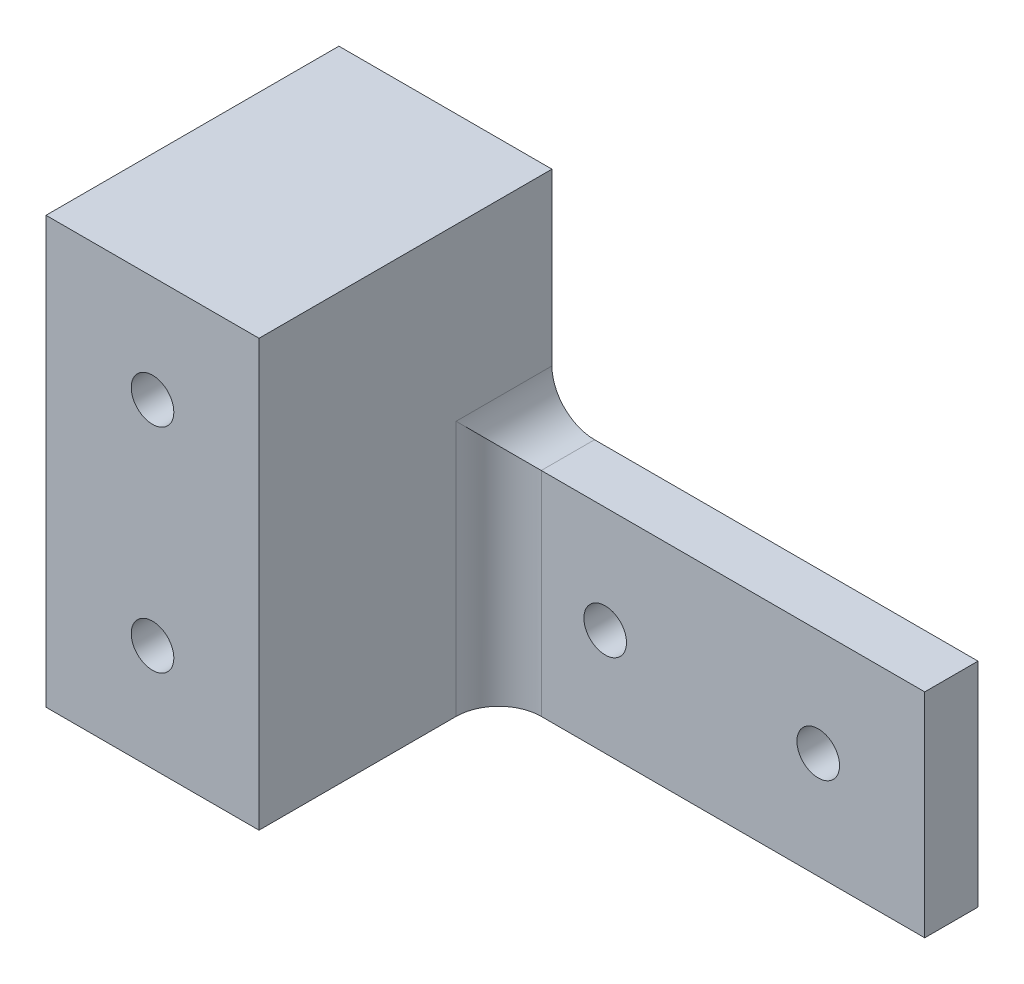
SolidWorks part; units mm, degrees
ref_plane "Front Plane" through (0, 0, 0) normal (0, 0, 1) x (1, 0, 0)
ref_plane "Top Plane" through (0, 0, 0) normal (0, 1, 0) x (1, 0, 0)
ref_plane "Right Plane" through (0, 0, 0) normal (1, 0, 0) x (0, 0, -1)
sketch "Sketch1" plane through (0, 0, 0) normal (0, 0, 1) x (1, 0, 0)
  line L0 (0, 0) -> (0, 50.8)
  line L1 (0, 50.8) -> (25.4, 50.8)
  line L2 (25.4, 50.8) -> (25.4, 25.4)
  line L3 (25.4, 25.4) -> (76.2, 25.4)
  line L4 (76.2, 25.4) -> (76.2, 0)
  line L5 (76.2, 0) -> (0, 0)
  dimension "D1" = 50.8
  dimension "D2" = 25.4
  dimension "3" = 76.2
extrude "Boss-Extrude1" add sketch "Sketch1" along normal blind 34.925
sketch "Sketch2" plane through (0, 0, 34.925) normal (0, 0, 1) x (1, 0, 0)
  line L0 (25.4, 50.8) -> (0, 50.8) construction
  line L1 (25.4, 25.4) -> (25.4, 50.8) construction
  line L2 (0, 0) -> (76.2, 0) construction
  circle A0 centre (12.7, 38.1) radius 2.54
  circle A1 centre (12.7, 12.7) radius 2.54
  circle A2 centre (38.1, 12.7) radius 2.54
  circle A3 centre (63.5, 12.7) radius 2.54
  dimension "D1" = 5.08
  dimension "D2" = 12.7
  dimension "D3" = 12.7
  dimension "D4" = 12.7
  dimension "D5" = 3
extrude "Cut-Extrude1" cut sketch "Sketch2" against normal through all
sketch "Sketch3" plane through (0, 0, 34.925) normal (0, 0, 1) x (1, 0, 0)
  line L0 (25.4, 50.8) -> (0, 50.8) construction
  line L1 (0, 0) -> (4.7625, 0)
  line L2 (0, 0) -> (0, 50.8)
  line L3 (0, 50.8) -> (4.7625, 50.8)
  line L4 (4.7625, 0) -> (4.7625, 50.8)
  dimension "D1" = 4.7625
sketch "Sketch4" plane through (0, 0, 0) normal (0, -1, 0) x (1, 0, 0)
  line L5 (76.2, 34.925) -> (25.4, 34.925)
  line L6 (76.2, 34.925) -> (76.2, 6.35)
  line L7 (76.2, 6.35) -> (25.4, 6.35)
  line L8 (25.4, 34.925) -> (25.4, 6.35)
  dimension "D1" = 28.575
  dimension "D2" = 50.8
extrude "Cut-Extrude3" cut sketch "Sketch4" against normal through all
fillet "Fillet1" radius 5.08 2 edges at (25.4, 25.4, 3.175) (25.4, 12.7, 6.35)
sketch "Sketch5" plane through (0, 0, 0) normal (0, 0, -1) x (-1, 0, 0)
  circle A0 centre (-12.7, 38.1) radius 4.445
  dimension "D1" = 8.89
extrude "Cut-Extrude4" cut sketch "Sketch5" against normal blind 22.225
